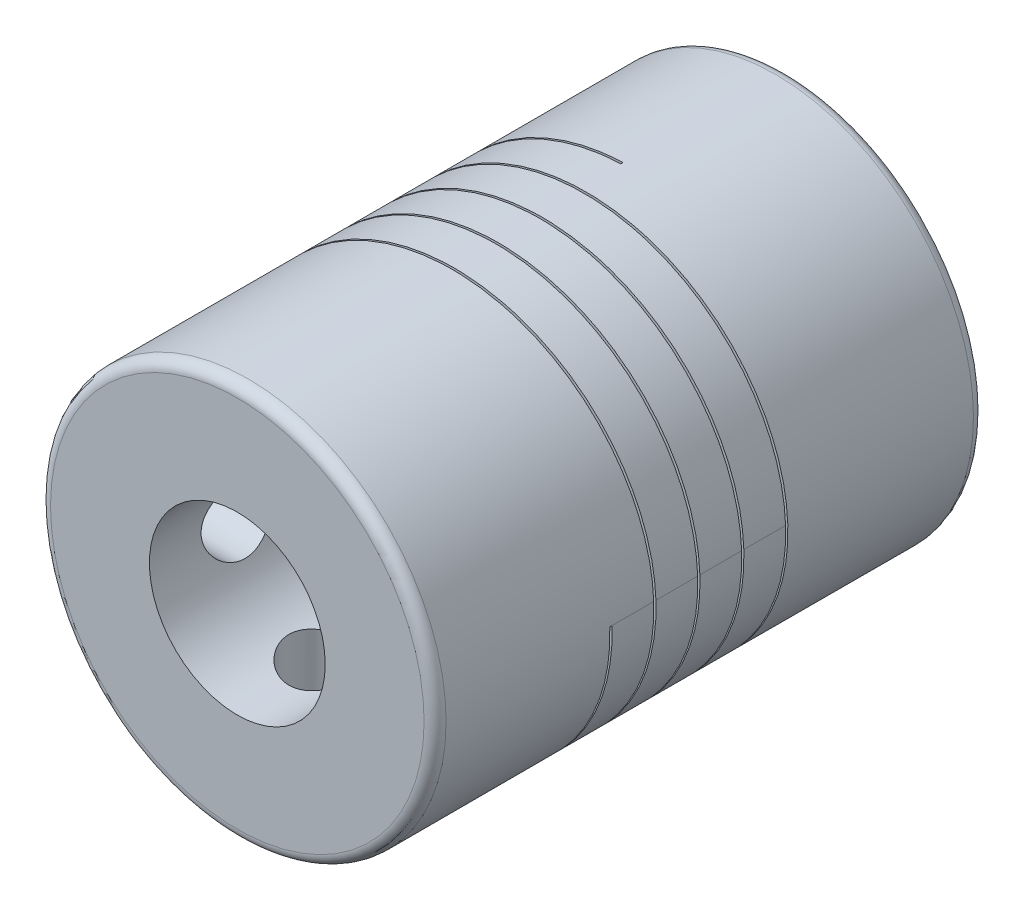
SolidWorks part; units mm, degrees
ref_plane "Front Plane" through (0, 0, 0) normal (0, 0, 1) x (1, 0, 0)
ref_plane "Top Plane" through (0, 0, 0) normal (0, 1, 0) x (1, 0, 0)
ref_plane "Right Plane" through (0, 0, 0) normal (1, 0, 0) x (0, 0, -1)
sketch "Sketch1" plane through (0, 0, 0) normal (0, 0, 1) x (1, 0, 0)
  circle A0 centre (0, 0) radius 9
  dimension "D1" = 18
extrude "Boss-Extrude1" add sketch "Sketch1" along normal blind 25
fillet "Fillet1" radius 0.5 2 edges at (9, 0, 0) (9, 0, 25)
sketch "Sketch2" plane through (0, 0, 25) normal (0, 0, 1) x (1, 0, 0)
  circle A0 centre (0, 0) radius 4
  dimension "D1" = 8
extrude "Cut-Extrude1" cut sketch "Sketch2" against normal blind 17
sketch "Sketch3" plane through (0, 0, 0) normal (0, 0, -1) x (-1, 0, 0)
  circle A0 centre (0, 0) radius 3
  dimension "D1" = 6
extrude "Cut-Extrude2" cut sketch "Sketch3" against normal through all
ref_plane "Plane2" through (0, 0, 17) normal (0, 0, 1) x (1, 0, 0)
sketch "Sketch6" plane through (0, 0, 17) normal (0, 0, 1) x (1, 0, 0)
  circle A0 centre (0, 0) radius 9
  circle A1 centre (0, 0) radius 9 construction
curve "Helix/Spiral2" pitch 2 height 9.5 turns 4.75
sketch "Sketch8" plane through (0, 0, 0) normal (0, 1, 0) x (1, 0, 0)
  line L0 (-9.35, -17) -> (9.35, -17) construction
  line L1 (17, -16.95) -> (1, -16.95)
  line L2 (17, -16.95) -> (17, -17.05)
  line L3 (17, -17.05) -> (1, -17.05)
  line L4 (1, -16.95) -> (1, -17.05)
  line L5 (17, -16.95) -> (1, -17.05) construction
  line L6 (17, -17.05) -> (1, -16.95) construction
  line L7 (9, -24.5) -> (9, -0.5) construction
  point P0 (9, -17)
  point P9 (9, -17.5)
  point P10 (9, -17.5)
  dimension "D1" = 0.1
  dimension "D2" = 16
sweep "Cut-Sweep1" cut profiles "Sketch8" path "Helix/Spiral2" align with end faces yes
ref_plane "Plane3" through (-9, 0, 0) normal (-1, 0, 0) x (0, 0, 1)
ref_plane "Plane4" through (0, -9, 0) normal (0, -1, 0) x (-1, 0, 0)
hole_wizard "M4 Tapped Hole1" positions "Sketch15" profile "Sketch11" tap size "M4" standard "ISO"
sketch "Sketch15" plane through (-9, 0, 0) normal (-1, 0, 0) x (0, 0, 1)
  line L0 (25, -8.5) -> (25, 8.5) construction
  line L1 (0, 8.5) -> (0, -8.5) construction
  point P0 (4, 0)
  point P2 (21, 0)
  dimension "D1" = 4
  dimension "D2" = 4
sketch "Sketch11" plane through (-9, 0, 4) normal (0, 1, 0) x (0, 0, 1)
  line L0 (0, 0) -> (0, 9.0914)
  line L1 (0, 9.0914) -> (1.65, 8.1)
  line L2 (1.65, 8.1) -> (1.65, 0)
  line L5 (1.65, 0) -> (0, 0)
  line L10 (0, 9.0914) -> (-1.65, 8.1) construction
  line L11 (0, -6.35) -> (0, 107.95) construction
  dimension "Tap Drill Dia." = 3.3
  dimension "Tap Drill Depth" = 8.1
  dimension "Drill Angle" = 118
cosmetic thread "Hole Thread1" parameters "D1"=5.3562, "D2"=4
cosmetic thread "Hole Thread2" parameters "D1"=6.4945, "D2"=4
hole_wizard "M4 Tapped Hole2" positions "Sketch17" profile "Sketch18" tap size "M4" standard "ISO"
sketch "Sketch17" plane through (0, -9, 0) normal (0, -1, 0) x (-1, 0, 0)
  line L0 (-4, -25) -> (4, -25) construction
  line L1 (8.5, 0) -> (-8.5, 0) construction
  point P0 (0, -21)
  point P2 (0, -4)
  point P9 (0, 0)
  dimension "D1" = 4
  dimension "D2" = 4
sketch "Sketch18" plane through (0, -9, 21) normal (1, 0, 0) x (0, 0, -1)
  line L0 (0, 0) -> (0, 9.0914)
  line L1 (0, 9.0914) -> (1.65, 8.1)
  line L2 (1.65, 8.1) -> (1.65, 0)
  line L5 (1.65, 0) -> (0, 0)
  line L10 (0, 9.0914) -> (-1.65, 8.1) construction
  line L11 (0, -6.35) -> (0, 107.95) construction
  dimension "Tap Drill Dia." = 3.3
  dimension "Tap Drill Depth" = 8.1
  dimension "Drill Angle" = 118
cosmetic thread "Hole Thread3" parameters "D1"=6.4945, "D2"=4
cosmetic thread "Hole Thread4" parameters "D1"=5.3562, "D2"=4
